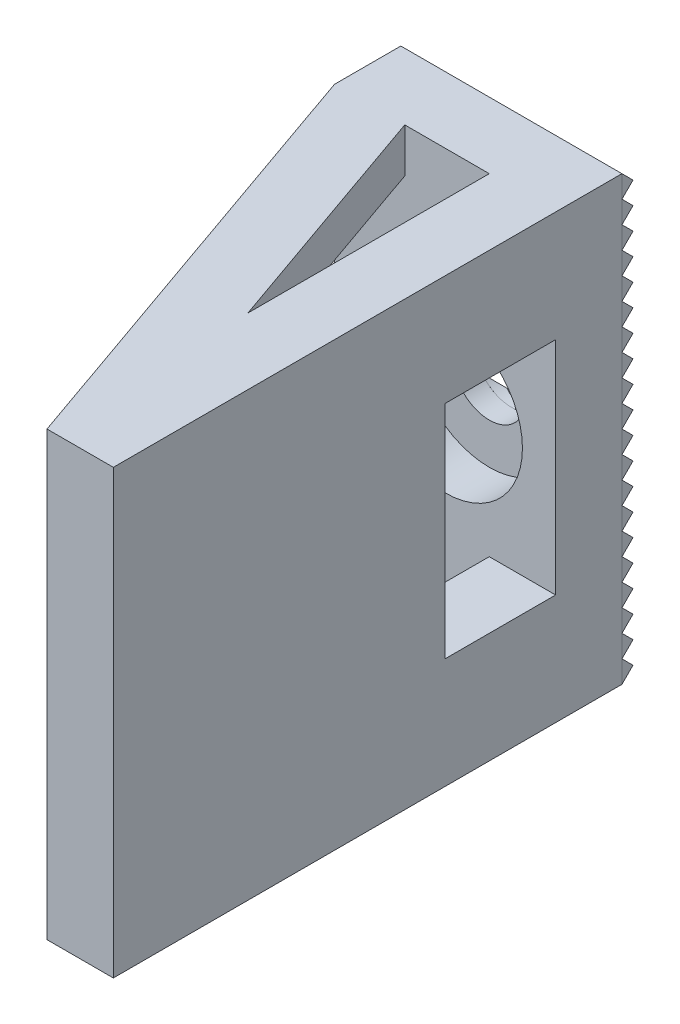
SolidWorks part; units mm, degrees
ref_plane "Front Plane" through (0, 0, 0) normal (0, 0, 1) x (1, 0, 0)
ref_plane "Top Plane" through (0, 0, 0) normal (0, 1, 0) x (1, 0, 0)
ref_plane "Right Plane" through (0, 0, 0) normal (1, 0, 0) x (0, 0, -1)
sketch "Sketch1" plane through (0, 0, 0) normal (0, 0, 1) x (1, 0, 0)
  line L1 (5, -10) -> (-5, -10)
  line L2 (5, -10) -> (5, 10)
  line L3 (5, 10) -> (-5, 10)
  line L4 (-5, -10) -> (-5, 10)
  line L5 (5, -10) -> (-5, 10) construction
  line L6 (5, 10) -> (-5, -10) construction
  point P0 (0, 0)
  dimension "D1" = 10
  dimension "D2" = 20
extrude "Boss-Extrude1" add sketch "Sketch1" along normal blind 3
sketch "Sketch2" plane through (0, 0, 3) normal (0, 0, 1) x (1, 0, 0)
  line L0 (-5, -10) -> (5, -10) construction
  line L1 (5, 10) -> (2, 10)
  line L2 (5, 10) -> (5, -10)
  line L3 (5, -10) -> (2, -10)
  line L4 (2, 10) -> (2, -10)
  dimension "D1" = 3
extrude "Boss-Extrude2" add sketch "Sketch2" along normal blind 20
sketch "Sketch3" plane through (0, -10, 0) normal (0, -1, 0) x (1, 0, 0)
  line L0 (2, 23) -> (-5, 3)
  line L1 (-5, 3) -> (-1.8216, 3)
  line L2 (-5, 3) -> (2, 3) construction
  line L3 (-1.8216, 3) -> (2, 13.9187)
  line L4 (2, 23) -> (2, 3) construction
  line L5 (2, 13.9187) -> (2, 23)
  dimension "D1" = 3
extrude "Boss-Extrude3" add sketch "Sketch3" against normal blind 2
extrude "Boss-Extrude4" add sketch "Sketch3<2>" along normal blind 2 from offset 20 offset against normal yes
sketch "Sketch3<2>" plane through (0, -10, 0) normal (0, -1, 0) x (1, 0, 0) same geometry as "Sketch3"
sketch "Sketch4" plane through (2, 0, 0) normal (-1, 0, 0) x (0, 0, 1)
  line L0 (3, 10) -> (3, -10) construction
  line L1 (3, 5) -> (8, 5)
  line L2 (3, 5) -> (3, -5)
  line L3 (3, -5) -> (8, -5)
  line L4 (8, 5) -> (8, -5)
  line L5 (23, 10) -> (3, 10) construction
  dimension "D1" = 10
  dimension "D2" = 5
  dimension "D3" = 5
extrude "Cut-Extrude1" cut sketch "Sketch4" against normal blind 12
sketch "Sketch5" plane through (5, 0, 0) normal (1, 0, 0) x (0, 0, -1)
  line L0 (0, 10) -> (0.5, 9.5)
  line L1 (0.5, 9.5) -> (0, 9)
  line L2 (0, -10) -> (0, 10) construction
  line L3 (0, 10) -> (0, 9)
  line L4 (0, 9) -> (0, 8)
  line L5 (0.5, 8.5) -> (0, 8)
  line L6 (0, 9) -> (0.5, 8.5)
  line L7 (0, 8) -> (0, 7)
  line L8 (0.5, 7.5) -> (0, 7)
  line L9 (0, 8) -> (0.5, 7.5)
  line L10 (0, 7) -> (0, 6)
  line L11 (0.5, 6.5) -> (0, 6)
  line L12 (0, 7) -> (0.5, 6.5)
  line L13 (0, 6) -> (0, 5)
  line L14 (0.5, 5.5) -> (0, 5)
  line L15 (0, 6) -> (0.5, 5.5)
  line L16 (0, 5) -> (0, 4)
  line L17 (0.5, 4.5) -> (0, 4)
  line L18 (0, 5) -> (0.5, 4.5)
  line L19 (0, 4) -> (0, 3)
  line L20 (0.5, 3.5) -> (0, 3)
  line L21 (0, 4) -> (0.5, 3.5)
  line L22 (0, 3) -> (0, 2)
  line L23 (0.5, 2.5) -> (0, 2)
  line L24 (0, 3) -> (0.5, 2.5)
  line L25 (0, 2) -> (0, 1)
  line L26 (0.5, 1.5) -> (0, 1)
  line L27 (0, 2) -> (0.5, 1.5)
  line L28 (0, 1) -> (0, 0)
  line L29 (0.5, 0.5) -> (0, 0)
  line L30 (0, 1) -> (0.5, 0.5)
  line L31 (0, 0) -> (0, -1)
  line L32 (0.5, -0.5) -> (0, -1)
  line L33 (0, 0) -> (0.5, -0.5)
  line L34 (0, -1) -> (0, -2)
  line L35 (0.5, -1.5) -> (0, -2)
  line L36 (0, -1) -> (0.5, -1.5)
  line L37 (0, -2) -> (0, -3)
  line L38 (0.5, -2.5) -> (0, -3)
  line L39 (0, -2) -> (0.5, -2.5)
  line L40 (0, -3) -> (0, -4)
  line L41 (0.5, -3.5) -> (0, -4)
  line L42 (0, -3) -> (0.5, -3.5)
  line L43 (0, -4) -> (0, -5)
  line L44 (0.5, -4.5) -> (0, -5)
  line L45 (0, -4) -> (0.5, -4.5)
  line L46 (0, -5) -> (0, -6)
  line L47 (0.5, -5.5) -> (0, -6)
  line L48 (0, -5) -> (0.5, -5.5)
  line L49 (0, -6) -> (0, -7)
  line L50 (0.5, -6.5) -> (0, -7)
  line L51 (0, -6) -> (0.5, -6.5)
  line L52 (0, -7) -> (0, -8)
  line L53 (0.5, -7.5) -> (0, -8)
  line L54 (0, -7) -> (0.5, -7.5)
  line L55 (0, -8) -> (0, -9)
  line L56 (0.5, -8.5) -> (0, -9)
  line L57 (0, -8) -> (0.5, -8.5)
  line L58 (0, -9) -> (0, -10)
  line L59 (0.5, -9.5) -> (0, -10)
  line L60 (0, -9) -> (0.5, -9.5)
  line M8 (0, -10) -> (0, 10)
  dimension "D1" = 1
  dimension "D2" = 90
  dimension "D3" = 20
extrude "Boss-Extrude9" add sketch "Sketch5" against normal up to surface (10 mm away) separate body contours L60 L59 M8 | L33 L32 M8 | L30 L29 M8 | L27 L26 M8 | L55 L56 L57 | L52 L53 L54 | L49 L50 L51 | L46 L47 L48 | L43 L44 L45 | L40 L41 L42 | L37 L38 L39 | L34 L35 L36 | L22 L23 L24 | L19 L20 L21 | L16 L17 L18 | L13 L14 L15 | L10 L11 L12 | L7 L8 L9 | L4 L5 L6 | L3 L1 L0 region at (5, -9.5, -0.1667) region at (5, -0.5, -0.1667) region at (5, 0.5, -0.1667) region at (5, 1.5, -0.1667) up to face at (-5, 0, 2)
sketch "Sketch6" plane through (0, 0, 3) normal (0, 0, 1) x (1, 0, 0)
  circle A0 centre (0, 0) radius 1.65
  dimension "D1" = 3.3
extrude "Cut-Extrude2" cut sketch "Sketch6" against normal blind 12
sketch "Sketch7" plane through (0, 0, 3) normal (0, 0, 1) x (1, 0, 0)
  circle A0 centre (0, 0) radius 3.5
  dimension "D1" = 7
extrude "Cut-Extrude3" cut sketch "Sketch7" against normal blind 2
